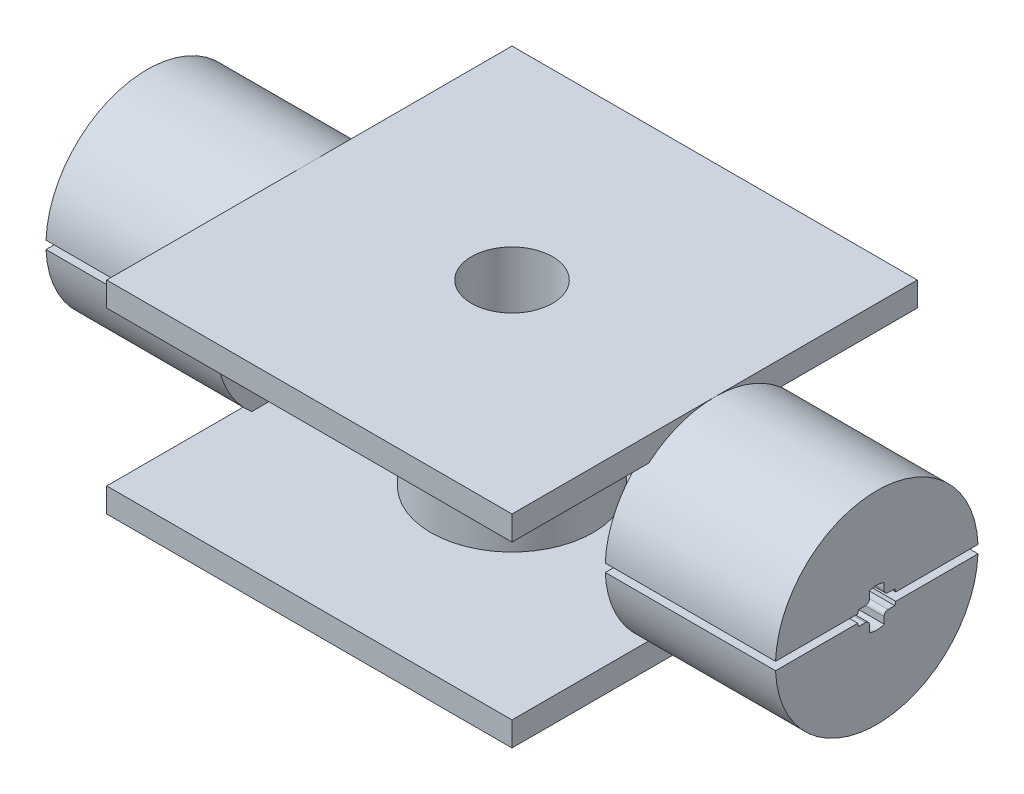
SolidWorks part; units mm, degrees
note: '?' marks a value the reader was unsure of.
ref_plane "Front Plane" through (0, 0, 0) normal (0, 0, 1) x (1, 0, 0)
ref_plane "Top Plane" through (0, 0, 0) normal (0, 1, 0) x (1, 0, 0)
ref_plane "Right Plane" through (0, 0, 0) normal (1, 0, 0) x (0, 0, -1)
sketch "Sketch1" plane through (0, 0, 0) normal (0, 1, 0) x (1, 0, 0)
  circle A0 centre (0, 0) radius 10
  dimension "D1" = 20
extrude "Boss-Extrude1" add sketch "Sketch1" along normal blind 19
sketch "Sketch3" plane through (0, 0, 0) normal (0, -1, 0) x (1, 0, 0)
  line L1 (-25, -25) -> (25, -25)
  line L2 (-25, -25) -> (-25, 25)
  line L3 (-25, 25) -> (25, 25)
  line L4 (25, -25) -> (25, 25)
  line L5 (-25, -25) -> (25, 25) construction
  line L6 (-25, 25) -> (25, -25) construction
  point P0 (0, 0)
  dimension "D1" = 50
  dimension "D2" = 50
extrude "Boss-Extrude2" add sketch "Sketch3" along normal blind 3
sketch "Sketch5" plane through (0, 19, 0) normal (0, 1, 0) x (1, 0, 0)
  line L1 (-25, -25) -> (25, -25)
  line L2 (-25, -25) -> (-25, 25)
  line L3 (-25, 25) -> (25, 25)
  line L4 (25, -25) -> (25, 25)
  line L5 (-25, -25) -> (25, 25) construction
  line L6 (-25, 25) -> (25, -25) construction
  point P0 (0, 0)
  dimension "D1" = 50
  dimension "D2" = 50
extrude "Boss-Extrude4" add sketch "Sketch5" along normal blind 3
sketch "Sketch6" plane through (0, 22, 0) normal (0, 1, 0) x (1, 0, 0)
  circle A0 centre (0, 0) radius 5
  dimension "D1" = 10
ref_axis "Axis1" through (-25, -3, 0) along (0, 1, 0)?
ref_axis "Axis2" through (25, 22, 0) along (0, -1, 0)?
sketch "Sketch7" plane through (-25, 0, 0) normal (-1, 0, 0) x (0, 0, 1)
  line L1 (0, 0) -> (0, 19)
  line L2 (-25, 19) -> (25, 19) construction
  circle A1 centre (0, 9.5) radius 12.5
  dimension "D1" = 25
extrude "Boss-Extrude5" add sketch "Sketch7" along normal blind 20 and the other way blind 1 contours A1
sketch "Sketch8" plane through (25, 0, 0) normal (1, 0, 0) x (0, 0, -1)
  line L0 (0, 0) -> (0, 19)
  line L1 (25, 0) -> (-25, 0) construction
  line L2 (-25, 19) -> (25, 19) construction
  circle A0 centre (0, 9.5) radius 10
  dimension "D1" = 20
extrude "Boss-Extrude6" add sketch "Sketch8" along normal blind 20 and the other way blind 1 contours A0
sketch "Sketch9" plane through (-45, 0, 0) normal (-1, 0, 0) x (0, 0, 1)
  line L1 (-14.4828, 9) -> (14.4828, 9)
  line L2 (-14.4828, 9) -> (-14.4828, 10)
  line L3 (-14.4828, 10) -> (14.4828, 10)
  line L4 (14.4828, 9) -> (14.4828, 10)
  line L5 (-14.4828, 9) -> (14.4828, 10) construction
  line L6 (-14.4828, 10) -> (14.4828, 9) construction
  point P0 (0, 9.5)
  dimension "D1" = 1
extrude "Cut-Extrude2" cut sketch "Sketch9" against normal up to surface (21 mm away) up to face at (-24, 9.5, 0)
sketch "Sketch10" plane through (45, 0, 0) normal (1, 0, 0) x (0, 0, -1)
  line L1 (-17.3427, 10) -> (17.3427, 10)
  line L2 (-17.3427, 10) -> (-17.3427, 9)
  line L3 (-17.3427, 9) -> (17.3427, 9)
  line L4 (17.3427, 10) -> (17.3427, 9)
  line L5 (-17.3427, 10) -> (17.3427, 9) construction
  line L6 (-17.3427, 9) -> (17.3427, 10) construction
  point P0 (0, 9.5)
  dimension "D1" = 1
extrude "Cut-Extrude3" cut sketch "Sketch10" against normal up to surface (21 mm away) up to face at (24, 9.5, 0)
extrude "Cut-Extrude4" cut sketch "Sketch6" against normal through all
sketch "Sketch11" plane through (-45, 0, 0) normal (-1, 0, 0) x (0, 0, 1)
  circle A0 centre (0, 9.5) radius 10.5
  circle A2 centre (0, 9.5) radius 12.5 construction
  dimension "D1" = 2
extrude "Cut-Extrude5" cut sketch "Sketch11" against normal offset from surface (13 mm away) 4 from offset 4 up to face at (-24, 4.2721, 0) offset against normal yes
other "SurfaceCut1" flip cut yes
mirror "Mirror2" about plane through (0, 0, 0) normal (1, 0, 0) of bodies 113
sketch "Sketch12" plane through (-45, 0, 0) normal (-1, 0, 0) x (0, 0, 1)
  line L0 (0, -986.0719) -> (0, 49013.9281) construction
  line L1 (-988.0978, 9.5) -> (49011.9022, 9.5) construction
  line L2 (12.49, 10) -> (-12.49, 10) construction
  line L3 (-12.49, 9) -> (12.49, 9) construction
  line L4 (0, -3) -> (0, 22) construction
  point P6 (0, 10)
  point P9 (0, 0)
  point P12 (0, 0)
  line B0 (-1.4, 10.4) -> (-2.2249, 10.4)
  line B1 (0.9, 7.2751) -> (0.9, 8.1)
  line B2 (-0.9, 7.2751) -> (-0.9, 8.1)
  line B3 (2.2249, 10.4) -> (1.4, 10.4)
  line B4 (2.2249, 8.6) -> (1.4, 8.6)
  line B5 (-0.9, 10.9) -> (-0.9, 11.7249)
  line B6 (0.9, 10.9) -> (0.9, 11.7249)
  line B7 (-1.4, 8.6) -> (-2.2249, 8.6)
  arc B8 (-2.2249, 10.4) -> (-2.2249, 8.6) centre (0, 9.5) ccw
  arc B9 (-1.4, 8.6) -> (-0.9, 8.1) centre (-1.4, 8.1) cw
  arc B10 (0.9, 8.1) -> (1.4, 8.6) centre (1.4, 8.1) cw
  arc B11 (1.4, 10.4) -> (0.9, 10.9) centre (1.4, 10.9) cw
  arc B12 (-0.9, 10.9) -> (-1.4, 10.4) centre (-1.4, 10.9) cw
  arc B13 (0.9, 11.7249) -> (-0.9, 11.7249) centre (0, 9.5) ccw
  arc B14 (2.2249, 8.6) -> (2.2249, 10.4) centre (0, 9.5) ccw
  arc B15 (-0.9, 7.2751) -> (0.9, 7.2751) centre (0, 9.5) ccw
sketch_block_instance "Axle Section Block-1"
sketch_block "Axle Section Block" parameters "D1"=4.8, "D3"=0.5, "D2"=1.8
extrude "Cut-Extrude6" cut sketch "Sketch12" against normal through all
